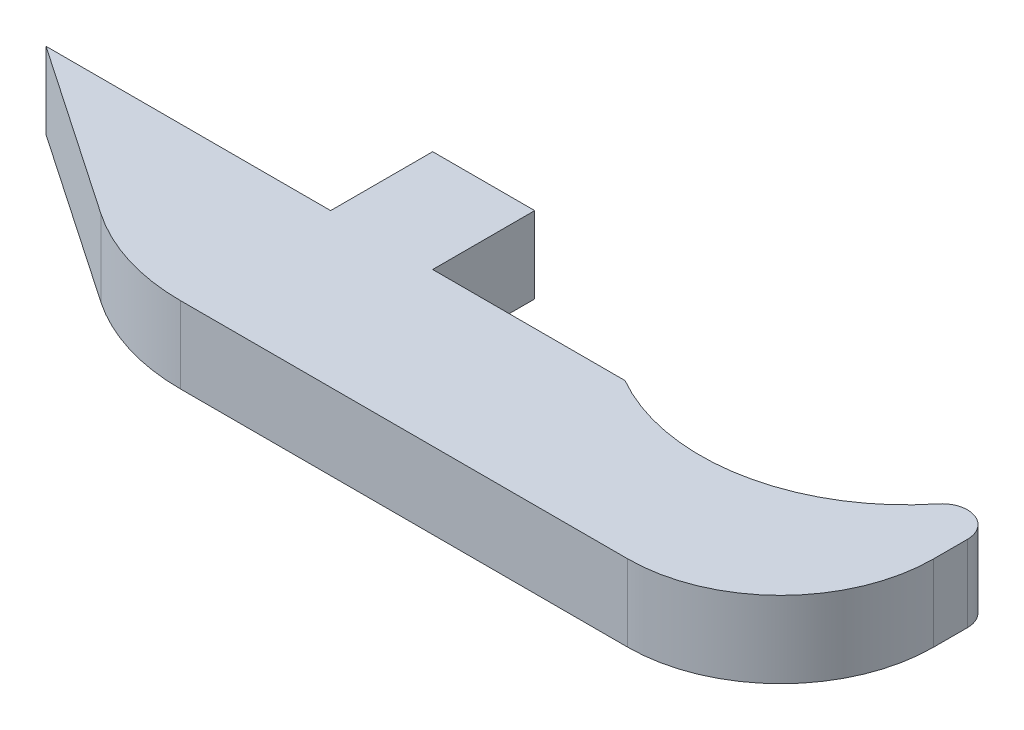
SolidWorks part; units mm, degrees
material "AISI 4130 Steel, annealed at 865C"
ref_plane "X-Y Datum" through (0, 0, 0) normal (0, 0, 1) x (1, 0, 0)
ref_plane "X-Z Datum" through (0, 0, 0) normal (0, 1, 0) x (1, 0, 0)
ref_plane "Y-Z Datum" through (0, 0, 0) normal (1, 0, 0) x (0, 0, -1)
sketch "Sketch1" plane through (0, 0, 0) normal (0, 1, 0) x (1, 0, 0)
  line L0 (20.8895, 0) -> (0, 0) construction
  line L1 (45.593, 0) -> (0, 0)
  line L2 (45.593, 0) -> (45.593, 11.1252)
  line L3 (17.145, -9.525) -> (58.42, -9.525)
  line L4 (58.42, 11.1252) -> (58.42, -9.525)
  line L5 (3.175, 0) -> (17.145, -9.525)
  circle A0 centre (45.593, 11.1252) radius 12.827
  dimension "D3" = 25.654
  dimension "D5" = 9.525
  dimension "D1" = 45.593
  dimension "D2" = 11.1252
  dimension "D4" = 3.175
  dimension "D6" = 41.275
extrude "Boss-Extrude1" add sketch "Sketch1" along normal blind 4.7625 contours L1 A0 region at (34.7653, 0, 4.3342)
fillet "Fillet1" radius 9.525 1 edges at (58.42, 2.3813, 9.525)
fillet "Fillet2" radius 1.5875 1 edges at (58.42, 2.3813, -11.1252)
fillet "Fillet4" radius 12.7 1 edges at (17.145, 2.3813, 9.525)
sketch "Sketch2" plane through (0, 0, 0) normal (0, -1, 0) x (1, 0, 0)
  line L1 (27.2395, -6.35) -> (27.2395, 0)
  line L2 (-7.0505, -6.35) -> (27.8745, -6.35) construction
  line L3 (27.2395, 0) -> (20.8895, 0)
  line L4 (27.2395, 0) -> (27.2395, -6.35)
  line L5 (27.2395, -6.35) -> (20.8895, -6.35)
  line L6 (20.8895, 0) -> (20.8895, -6.35)
  line L7 (33.5895, 0) -> (33.5895, -6.35) construction
  line M6 (3.175, 0) -> (39.2085, 0)
  dimension "D1" = 6.35
  dimension "D2" = 6.35
extrude "Boss-Extrude2" add sketch "Sketch2" against normal blind 4.7625 contours L6 L5 L1 M6 region at (24.0645, 0, -3.175)
